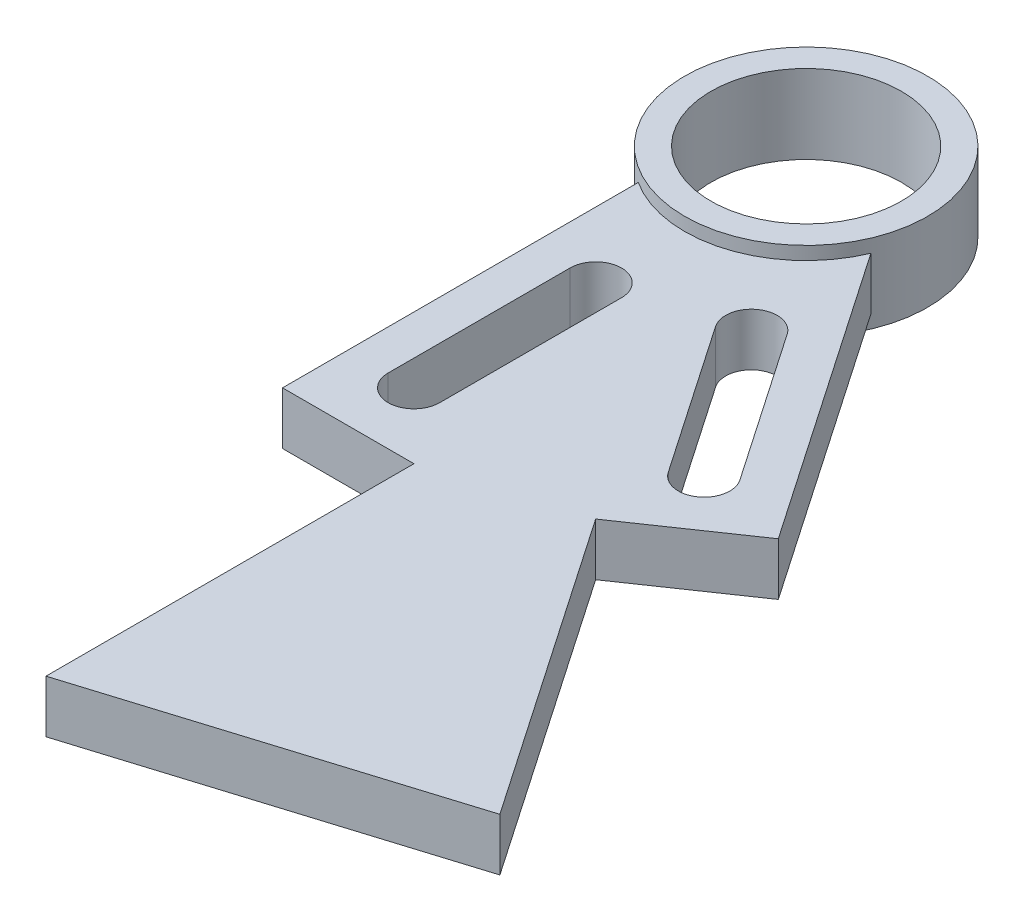
SolidWorks part; units mm, degrees
material "AISI 4130 Steel, normalized at 870C"
ref_plane "Front Plane" through (0, 0, 0) normal (0, 0, 1) x (1, 0, 0)
ref_plane "Top Plane" through (0, 0, 0) normal (0, 1, 0) x (1, 0, 0)
ref_plane "Right Plane" through (0, 0, 0) normal (1, 0, 0) x (0, 0, -1)
sketch "Sketch1" plane through (0, 0, 0) normal (0, 1, 0) x (1, 0, 0)
  line L0 (0, -50.4952) -> (0, -14.6812) construction
  line L1 (28.5244, -41.6668) -> (8.2933, -12.1144) construction
  line L2 (0, -47.3837) -> (0, -25.4127) construction
  line L5 (-3.1115, -47.3837) -> (-3.1115, -25.4127)
  line L8 (-7.9375, -55.3212) -> (7.9375, -55.3212)
  line L9 (24.7009, -50.1329) -> (37.8003, -41.1652)
  line L10 (-7.9375, -55.3212) -> (-7.9375, -12.3505)
  line L11 (37.8003, -41.1652) -> (13.5264, -5.7073)
  line L12 (7.9375, -55.3212) -> (7.9375, -99.7712)
  line L13 (24.7009, -50.1329) -> (49.8104, -86.8114)
  line L14 (7.9375, -99.7712) -> (49.8104, -86.8114)
  line L15 (0, -14.6812) -> (0, 0) construction
  line L16 (0, -55.3212) -> (0, -50.4952) construction
  line L17 (31.2506, -45.6491) -> (28.5244, -41.6668)
  line L18 (3.1115, -47.3837) -> (3.1115, -25.4127)
  line L19 (14.3555, -20.9696) -> (26.7667, -39.0993) construction
  line L20 (16.923, -19.212) -> (29.3342, -37.3416)
  line L21 (11.788, -22.7273) -> (24.1992, -40.857)
  line L22 (8.2933, -12.1144) -> (0, 0) construction
  line L23 (0, 0) -> (19.5258, -63.0875) construction
  line L25 (173.071, -252.8121) -> (14.4872, -21.1621) construction
  line L27 (0, 0) -> (28.8739, -93.2913) construction
  circle A0 centre (0, 0) radius 11.5062
  circle A1 centre (0, 0) radius 14.6812
  arc A2 (-3.1115, -47.3837) -> (3.1115, -47.3837) centre (0, -47.3837) ccw
  arc A3 (3.1115, -25.4127) -> (-3.1115, -25.4127) centre (0, -25.4127) ccw
  arc A4 (16.923, -19.212) -> (11.788, -22.7273) centre (14.3555, -20.9696) ccw
  arc A5 (24.1992, -40.857) -> (29.3342, -37.3416) centre (26.7667, -39.0993) ccw
  point P9 (0, -36.3982)
  point P14 (20.5611, -30.0345)
  point P23 (0, -55.3212)
  point P26 (31.2506, -45.6491)
  point P33 (0, -50.4952)
  point P36 (28.5244, -41.6668)
  point P38 (0, -22.3012)
  dimension "D2" = 29.3624
  dimension "D3" = 40.64
  dimension "D4" = 4.826
  dimension "D6" = 44.45
  dimension "D7" = 7.9375
  dimension "D5" = 4.826
  dimension "D8" = 7.62
  dimension "D9" = 66.04
extrude "Bearing extrude" add sketch "Sketch1" along normal mid plane 9.525 contours A1 A0 region at (-6.8368, 0, -12.521)
extrude "Boss-Extrude2" add sketch "Sketch1<5>" along normal mid plane 6.35 contours A1 L10 L8 L12 L14 L13 L9 L11 A4 A2 region at (17.3599, 0, 56.0897)
sketch "Sketch1<5>" plane through (0, 0, 0) normal (0, 1, 0) x (1, 0, 0) same geometry as "Sketch1"
sketch3d "Tab Point"
  line L0 (19.5258, 0, 63.0875) -> (19.5258, 25.4, 63.0875) construction
  line L1 (0, 0, 0) -> (19.5258, 0, 63.0875) construction
  line L2 (0, 0, 0) -> (28.8739, 0, 93.2913) construction
  dimension "D1" = 25.4
equation "\"Apex_thickness\"= .25"
equation "\"Bearing_diameter\"= .906"
equation "\"A-arm_angle\"= 32.91"
equation "\"D1@Sketch1\"=\"Bearing_diameter\""
equation "\"D1@Boss-Extrude2\"= \"Apex_thickness\""
equation "\"apex slot\"= 1.4"
equation "\"tube diameter\"= 5 / 8"
